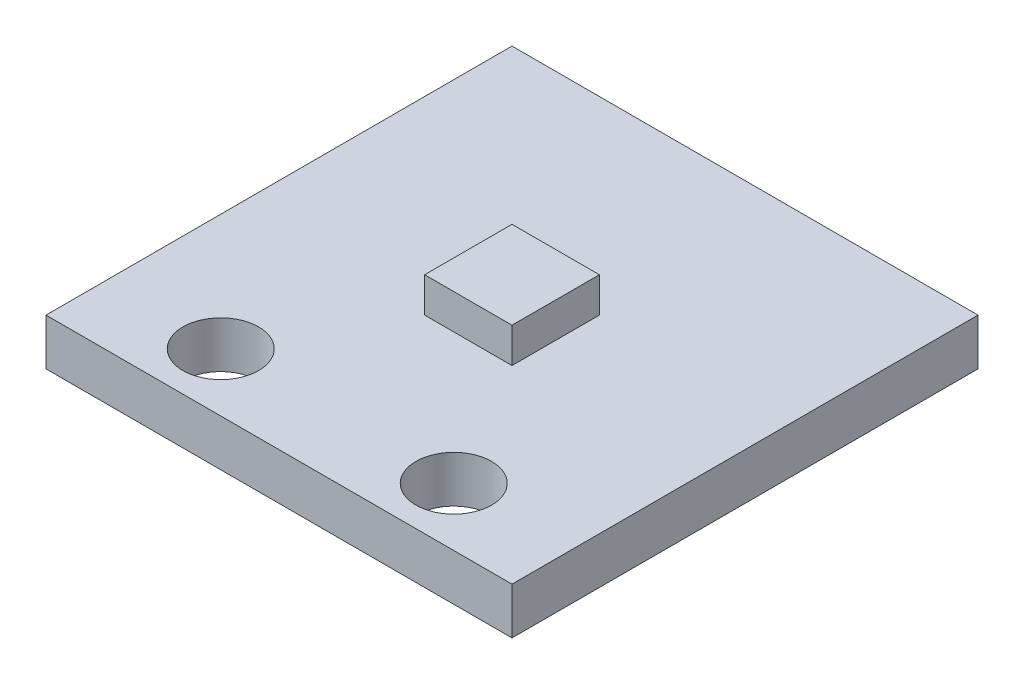
SolidWorks part; units mm, degrees
ref_plane "前视基准面" through (0, 0, 0) normal (0, 0, 1) x (1, 0, 0)
ref_plane "上视基准面" through (0, 0, 0) normal (0, 1, 0) x (1, 0, 0)
ref_plane "右视基准面" through (0, 0, 0) normal (1, 0, 0) x (0, 0, -1)
other "Configuration Table"
sketch "草图1" plane through (0, 0, 0) normal (0, 0, 1) x (1, 0, 0)
  line L1 (-138, 143) -> (-122, 143)
  line L2 (-138, 143) -> (-138, 146)
  line L3 (-138, 146) -> (-122, 146)
  line L4 (-122, 143) -> (-122, 146)
extrude "SHT40_by_rear_vent" [suppressed] add sketch "草图1" along normal blind 16 from offset 54
sketch "草图2" plane through (0, 0, 0) normal (0, 0, 1) x (1, 0, 0)
  line L1 (-130, 132.4) -> (-114, 132.4)
  line L2 (-130, 132.4) -> (-130, 134)
  line L3 (-130, 134) -> (-114, 134)
  line L4 (-114, 132.4) -> (-114, 134)
extrude "V10_SHT_candidate_carrier16x16" add sketch "草图2" along normal blind 16 from offset 54
sketch "草图3" plane through (0, 0, 0) normal (0, 0, 1) x (1, 0, 0)
  line L1 (-123.5, 134) -> (-120.5, 134)
  line L2 (-123.5, 134) -> (-123.5, 135.2)
  line L3 (-123.5, 135.2) -> (-120.5, 135.2)
  line L4 (-120.5, 134) -> (-120.5, 135.2)
extrude "V10_SHT_sensing_package_rearward" add sketch "草图3" along normal blind 3 from offset 60.5
sketch "草图4" plane through (0, 132.4, 0) normal (0, -1, 0) x (1, 0, 0)
  circle A0 centre (-126, 68) radius 1.3
  circle A1 centre (-118, 68) radius 1.3
extrude "V10_SHT_two_candidate_holes8mm" cut sketch "草图4" against normal blind 1.6
